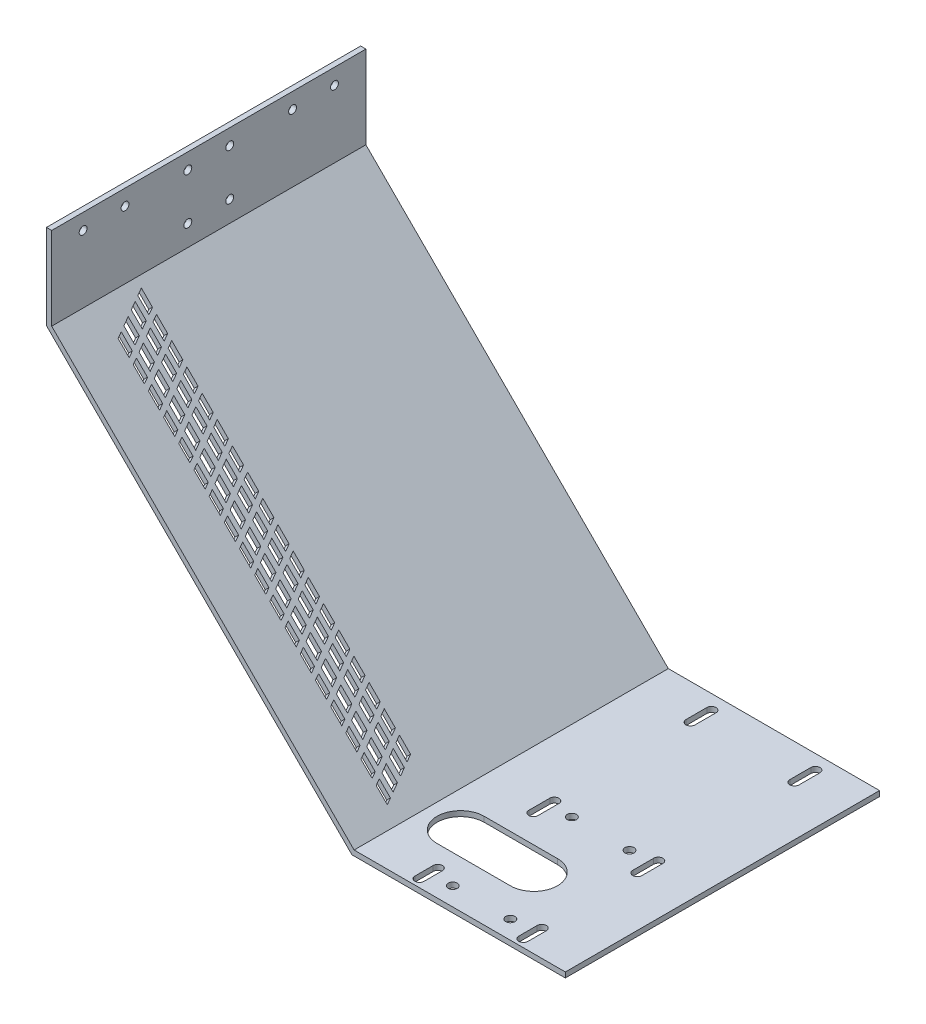
SolidWorks part; units mm, degrees
ref_plane "前视基准面" through (0, 0, 0) normal (0, 0, 1) x (1, 0, 0)
ref_plane "上视基准面" through (0, 0, 0) normal (0, 1, 0) x (1, 0, 0)
ref_plane "右视基准面" through (0, 0, 0) normal (1, 0, 0) x (0, 0, -1)
other "Configuration Table"
sketch "草图1" plane through (0, 0, 0) normal (0, 0, 1) x (1, 0, 0)
  line L0 (-1, -199.1726) -> (-1, -50)
  line L1 (-1, -50) -> (-199.1726, -50)
  line L2 (-199.1726, -50) -> (-199.1726, -82.5)
  line L3 (-199.1726, -82.5) -> (-82.5, -199.1726)
  line L4 (-82.5, -199.1726) -> (-1, -199.1726)
  dimension "D1" = 116.6726
  dimension "D2" = 198.1726
  dimension "D3" = 116.6726
  dimension "D4" = 149.1726
extrude "凸台-拉伸1" add sketch "草图1" against normal blind 120
sketch "草图2" plane through (0, 0, -120) normal (0, 0, -1) x (-1, 0, 0)
  line L0 (197.1726, -81.6716) -> (197.1726, -50)
  line L1 (197.1726, -50) -> (1, -50)
  line L2 (1, -50) -> (1, -197.1726)
  line L3 (1, -197.1726) -> (81.6716, -197.1726)
  line L4 (81.6716, -197.1726) -> (197.1726, -81.6716)
  line L5 (199.1726, -50) -> (199.1726, -82.5) construction
  line L6 (82.5, -199.1726) -> (1, -199.1726) construction
  dimension "D1" = 2
  dimension "D2" = 117.501
  dimension "D3" = 198.1726
  dimension "D4" = 2
  dimension "D5" = 117.501
  dimension "D6" = 149.1726
extrude "切除-拉伸1" cut sketch "草图2" against normal through all
sketch "草图3" plane through (0, -197.1726, 0) normal (0, 1, 0) x (-1, 0, 0)
  line L0 (57.95, -106.5) -> (57.95, -114.5)
  line L1 (61.45, -114.5) -> (61.45, -106.5)
  line L2 (81.6716, 0) -> (81.6716, -120) construction
  line L3 (1, -120) -> (81.6716, -120) construction
  arc A0 (61.45, -106.5) -> (57.95, -106.5) centre (59.7, -106.5) ccw
  arc A1 (57.95, -114.5) -> (61.45, -114.5) centre (59.7, -114.5) ccw
  dimension "D1" = 1.75
  dimension "D2" = 21.9716
  dimension "D3" = 5.5
  dimension "D4" = 13.5
extrude "切除-拉伸2" cut sketch "草图3" against normal through all
sketch "草图4" plane through (0, -197.1726, 0) normal (0, 1, 0) x (-1, 0, 0)
  line L0 (18.25, -106.5) -> (18.25, -114.5)
  line L1 (21.75, -114.5) -> (21.75, -106.5)
  line L2 (61.45, -114.5) -> (61.45, -106.5) construction
  arc A0 (18.25, -114.5) -> (21.75, -114.5) centre (20, -114.5) ccw
  arc A1 (21.75, -106.5) -> (18.25, -106.5) centre (20, -106.5) ccw
  dimension "D1" = 1.75
  dimension "D2" = 41.45
  dimension "D3" = 8
extrude "切除-拉伸3" cut sketch "草图4" against normal through all
sketch "草图5" plane through (0, -197.1726, 0) normal (0, 1, 0) x (-1, 0, 0)
  line L0 (61.45, -54.5) -> (61.45, -46.5)
  line L1 (57.95, -46.5) -> (57.95, -54.5)
  line L2 (18.25, -106.5) -> (18.25, -114.5) construction
  arc A0 (61.45, -46.5) -> (57.95, -46.5) centre (59.7, -46.5) ccw
  arc A1 (57.95, -54.5) -> (61.45, -54.5) centre (59.7, -54.5) ccw
  dimension "D1" = 1.75
  dimension "D2" = 41.45
  dimension "D3" = 52
  dimension "D4" = 60
extrude "切除-拉伸4" cut sketch "草图5" against normal through all
sketch "草图6" plane through (0, -197.1726, 0) normal (0, 1, 0) x (-1, 0, 0)
  line L0 (21.75, -54.5) -> (21.75, -46.5)
  line L1 (18.25, -46.5) -> (18.25, -54.5)
  line L2 (61.45, -54.5) -> (61.45, -46.5) construction
  arc A0 (18.25, -54.5) -> (21.75, -54.5) centre (20, -54.5) ccw
  arc A1 (21.75, -46.5) -> (18.25, -46.5) centre (20, -46.5) ccw
  dimension "D1" = 1.75
  dimension "D2" = 41.45
  dimension "D3" = 52
  dimension "D4" = 60
extrude "切除-拉伸5" cut sketch "草图6" against normal through all
sketch "草图7" plane through (0, -197.1726, 0) normal (0, 1, 0) x (-1, 0, 0)
  line L0 (61.45, -10) -> (61.45, -3)
  line L1 (57.95, -3) -> (57.95, -10)
  line L2 (61.45, -54.5) -> (61.45, -46.5) construction
  arc A0 (61.45, -3) -> (57.95, -3) centre (59.7, -3) ccw
  arc A1 (57.95, -10) -> (61.45, -10) centre (59.7, -10) ccw
  dimension "D1" = 1.75
  dimension "D2" = 1.75
  dimension "D3" = 96.5
  dimension "D4" = 103.5
extrude "切除-拉伸6" cut sketch "草图7" against normal through all
sketch "草图8" plane through (0, -197.1726, 0) normal (0, 1, 0) x (-1, 0, 0)
  line L0 (18.25, -3) -> (18.25, -10)
  line L1 (21.75, -10) -> (21.75, -3)
  line L2 (61.45, -54.5) -> (61.45, -46.5) construction
  arc A0 (18.25, -10) -> (21.75, -10) centre (20, -10) ccw
  arc A1 (21.75, -3) -> (18.25, -3) centre (20, -3) ccw
  dimension "D1" = 1.75
  dimension "D2" = 41.45
  dimension "D3" = 44.5
  dimension "D4" = 51.5
extrude "切除-拉伸7" cut sketch "草图8" against normal through all
sketch "草图9" plane through (-139.4221, -139.4221, 0) normal (0.7071, 0.7071, 0) x (-0.7071, 0.7071, 0)
  line L0 (-55.0094, -28) -> (-56.4528, -25.5)
  line L1 (-56.4528, -25.5) -> (-62.4528, -25.5)
  line L2 (-62.4528, -25.5) -> (-61.0094, -28)
  line L3 (-61.0094, -28) -> (-55.0094, -28)
  line L4 (81.6716, 0) -> (81.6716, -120) construction
  dimension "D1" = 136.681
  dimension "D2" = 138.1243
  dimension "D3" = 142.681
  dimension "D4" = 144.1243
  dimension "D5" = 25.5
  dimension "D6" = 28
extrude "切除-拉伸8" cut sketch "草图9" against normal through all
sketch "草图10" plane through (-139.4221, -139.4221, 0) normal (0.7071, 0.7071, 0) x (-0.7071, 0.7071, 0)
  line L0 (-57.6075, -23.5) -> (-59.2056, -20.7321)
  line L1 (-59.2056, -20.7321) -> (-65.2056, -20.7321)
  line L2 (-65.2056, -20.7321) -> (-63.6075, -23.5)
  line L3 (-63.6075, -23.5) -> (-57.6075, -23.5)
  dimension "D1" = 2.5981
  dimension "D2" = 4.1962
  dimension "D3" = 8.5981
  dimension "D4" = 10.1962
  dimension "D5" = 2
  dimension "D6" = 4.7679
extrude "切除-拉伸9" cut sketch "草图10" against normal through all
sketch "草图11" plane through (-139.4221, -139.4221, 0) normal (0.7071, 0.7071, 0) x (-0.7071, 0.7071, 0)
  line L0 (-51.8094, -29.7321) -> (-50.5, -32)
  line L1 (-50.5, -32) -> (-44.5, -32)
  line L2 (-44.5, -32) -> (-45.8094, -29.7321)
  line L3 (-45.8094, -29.7321) -> (-51.8094, -29.7321)
  dimension "D1" = 13.3962
  dimension "D2" = 14.7056
  dimension "D3" = 19.3962
  dimension "D4" = 20.7056
  dimension "D5" = 1.7321
  dimension "D6" = 4
extrude "切除-拉伸10" cut sketch "草图11" against normal through all
sketch "草图12" plane through (-139.4221, -139.4221, 0) normal (0.7071, 0.7071, 0) x (-0.7071, 0.7071, 0)
  line L0 (-46.8094, -28) -> (-48.2528, -25.5)
  line L1 (-48.2528, -25.5) -> (-54.2528, -25.5)
  line L2 (-54.2528, -25.5) -> (-52.8094, -28)
  line L3 (-52.8094, -28) -> (-46.8094, -28)
  dimension "D1" = 2.3094
  dimension "D2" = 3.7528
  dimension "D3" = 8.3094
  dimension "D4" = 9.7528
  dimension "D5" = 4.7679
  dimension "D6" = 7.2679
extrude "切除-拉伸11" cut sketch "草图12" against normal through all
sketch "草图13" plane through (-139.4221, -139.4221, 0) normal (0.7071, 0.7071, 0) x (-0.7071, 0.7071, 0)
  line L0 (-49.4075, -23.5) -> (-51.0056, -20.7321)
  line L1 (-51.0056, -20.7321) -> (-57.0056, -20.7321)
  line L2 (-57.0056, -20.7321) -> (-55.4075, -23.5)
  line L3 (-55.4075, -23.5) -> (-49.4075, -23.5)
  dimension "D1" = 6.6019
  dimension "D2" = 8.2
  dimension "D3" = 12.6019
  dimension "D4" = 14.2
  dimension "D5" = 8.5
  dimension "D6" = 11.2679
extrude "切除-拉伸12" cut sketch "草图13" against normal through all
sketch "草图14" plane through (-139.4221, -139.4221, 0) normal (0.7071, 0.7071, 0) x (-0.7071, 0.7071, 0)
  line L0 (-43.6094, -29.7321) -> (-42.3, -32)
  line L1 (-42.3, -32) -> (-36.3, -32)
  line L2 (-36.3, -32) -> (-37.6094, -29.7321)
  line L3 (-37.6094, -29.7321) -> (-43.6094, -29.7321)
  dimension "D1" = 0.8906
  dimension "D2" = 2.2
  dimension "D3" = 6.8906
  dimension "D4" = 8.2
  dimension "D5" = 9
  dimension "D6" = 11.2679
extrude "切除-拉伸13" cut sketch "草图14" against normal through all
sketch "草图15" plane through (-139.4221, -139.4221, 0) normal (0.7071, 0.7071, 0) x (-0.7071, 0.7071, 0)
  line L0 (-38.6094, -28) -> (-40.0528, -25.5)
  line L1 (-40.0528, -25.5) -> (-46.0528, -25.5)
  line L2 (-46.0528, -25.5) -> (-44.6094, -28)
  line L3 (-44.6094, -28) -> (-38.6094, -28)
  dimension "D1" = 10.9528
  dimension "D2" = 12.3962
  dimension "D3" = 16.9528
  dimension "D4" = 18.3962
  dimension "D5" = 4
  dimension "D6" = 6.5
extrude "切除-拉伸14" cut sketch "草图15" against normal through all
sketch "草图16" plane through (-139.4221, -139.4221, 0) normal (0.7071, 0.7071, 0) x (-0.7071, 0.7071, 0)
  line L0 (-41.2075, -23.5) -> (-42.8056, -20.7321)
  line L1 (-42.8056, -20.7321) -> (-48.8056, -20.7321)
  line L2 (-48.8056, -20.7321) -> (-47.2075, -23.5)
  line L3 (-47.2075, -23.5) -> (-41.2075, -23.5)
  dimension "D1" = 4.9075
  dimension "D2" = 6.5056
  dimension "D3" = 10.9075
  dimension "D4" = 12.5056
  dimension "D5" = 2.7679
extrude "切除-拉伸15" cut sketch "草图16" against normal through all
sketch "草图17" plane through (-139.4221, -139.4221, 0) normal (0.7071, 0.7071, 0) x (-0.7071, 0.7071, 0)
  line L0 (-35.4094, -29.7321) -> (-34.1, -32)
  line L1 (-34.1, -32) -> (-28.1, -32)
  line L2 (-28.1, -32) -> (-29.4094, -29.7321)
  line L3 (-29.4094, -29.7321) -> (-35.4094, -29.7321)
  dimension "D1" = 21.5962
  dimension "D2" = 22.9056
  dimension "D3" = 27.5962
  dimension "D4" = 28.9056
  dimension "D5" = 2.2679
extrude "切除-拉伸16" cut sketch "草图17" against normal through all
sketch "草图18" plane through (-139.4221, -139.4221, 0) normal (0.7071, 0.7071, 0) x (-0.7071, 0.7071, 0)
  line L0 (-30.4094, -28) -> (-31.8528, -25.5)
  line L1 (-31.8528, -25.5) -> (-37.8528, -25.5)
  line L2 (-37.8528, -25.5) -> (-36.4094, -28)
  line L3 (-36.4094, -28) -> (-30.4094, -28)
  dimension "D1" = 2.3094
  dimension "D2" = 3.7528
  dimension "D3" = 8.3094
  dimension "D4" = 9.7528
  dimension "D5" = 4.7679
  dimension "D6" = 7.2679
extrude "切除-拉伸17" cut sketch "草图18" against normal through all
sketch "草图19" plane through (-139.4221, -139.4221, 0) normal (0.7071, 0.7071, 0) x (-0.7071, 0.7071, 0)
  line L0 (-33.0075, -23.5) -> (-34.6056, -20.7321)
  line L1 (-34.6056, -20.7321) -> (-40.6056, -20.7321)
  line L2 (-40.6056, -20.7321) -> (-39.0075, -23.5)
  line L3 (-39.0075, -23.5) -> (-33.0075, -23.5)
  dimension "D1" = 14.8019
  dimension "D2" = 16.4
  dimension "D3" = 20.8019
  dimension "D4" = 22.4
  dimension "D5" = 8.5
  dimension "D6" = 11.2679
extrude "切除-拉伸18" cut sketch "草图19" against normal through all
sketch "草图20" plane through (-139.4221, -139.4221, 0) normal (0.7071, 0.7071, 0) x (-0.7071, 0.7071, 0)
  line L0 (-27.2094, -29.7321) -> (-25.9, -32)
  line L1 (-25.9, -32) -> (-19.9, -32)
  line L2 (-19.9, -32) -> (-21.2094, -29.7321)
  line L3 (-21.2094, -29.7321) -> (-27.2094, -29.7321)
  dimension "D1" = 0.8906
  dimension "D2" = 2.2
  dimension "D3" = 6.8906
  dimension "D4" = 8.2
  dimension "D5" = 9
  dimension "D6" = 11.2679
extrude "切除-拉伸19" cut sketch "草图20" against normal through all
sketch "草图21" plane through (-139.4221, -139.4221, 0) normal (0.7071, 0.7071, 0) x (-0.7071, 0.7071, 0)
  line L0 (-22.2094, -28) -> (-23.6528, -25.5)
  line L1 (-23.6528, -25.5) -> (-29.6528, -25.5)
  line L2 (-29.6528, -25.5) -> (-28.2094, -28)
  line L3 (-28.2094, -28) -> (-22.2094, -28)
  dimension "D1" = 19.1528
  dimension "D2" = 20.5962
  dimension "D3" = 25.1528
  dimension "D4" = 26.5962
  dimension "D5" = 4
  dimension "D6" = 6.5
extrude "切除-拉伸20" cut sketch "草图21" against normal through all
sketch "草图22" plane through (-139.4221, -139.4221, 0) normal (0.7071, 0.7071, 0) x (-0.7071, 0.7071, 0)
  line L0 (-24.8075, -23.5) -> (-26.4056, -20.7321)
  line L1 (-26.4056, -20.7321) -> (-32.4056, -20.7321)
  line L2 (-32.4056, -20.7321) -> (-30.8075, -23.5)
  line L3 (-30.8075, -23.5) -> (-24.8075, -23.5)
  dimension "D1" = 4.9075
  dimension "D2" = 6.5056
  dimension "D3" = 10.9075
  dimension "D4" = 12.5056
  dimension "D5" = 2.7679
extrude "切除-拉伸21" cut sketch "草图22" against normal through all
sketch "草图23" plane through (-139.4221, -139.4221, 0) normal (0.7071, 0.7071, 0) x (-0.7071, 0.7071, 0)
  line L0 (-19.0094, -29.7321) -> (-17.7, -32)
  line L1 (-17.7, -32) -> (-11.7, -32)
  line L2 (-11.7, -32) -> (-13.0094, -29.7321)
  line L3 (-13.0094, -29.7321) -> (-19.0094, -29.7321)
  dimension "D1" = 29.7962
  dimension "D2" = 31.1056
  dimension "D3" = 35.7962
  dimension "D4" = 37.1056
  dimension "D5" = 2.2679
extrude "切除-拉伸22" cut sketch "草图23" against normal through all
sketch "草图24" plane through (-139.4221, -139.4221, 0) normal (0.7071, 0.7071, 0) x (-0.7071, 0.7071, 0)
  line L0 (-14.0094, -28) -> (-15.4528, -25.5)
  line L1 (-15.4528, -25.5) -> (-21.4528, -25.5)
  line L2 (-21.4528, -25.5) -> (-20.0094, -28)
  line L3 (-20.0094, -28) -> (-14.0094, -28)
  dimension "D1" = 2.3094
  dimension "D2" = 3.7528
  dimension "D3" = 8.3094
  dimension "D4" = 9.7528
  dimension "D5" = 4.7679
  dimension "D6" = 7.2679
extrude "切除-拉伸23" cut sketch "草图24" against normal through all
sketch "草图25" plane through (-139.4221, -139.4221, 0) normal (0.7071, 0.7071, 0) x (-0.7071, 0.7071, 0)
  line L0 (-16.6075, -23.5) -> (-18.2056, -20.7321)
  line L1 (-18.2056, -20.7321) -> (-24.2056, -20.7321)
  line L2 (-24.2056, -20.7321) -> (-22.6075, -23.5)
  line L3 (-22.6075, -23.5) -> (-16.6075, -23.5)
  dimension "D1" = 23.0019
  dimension "D2" = 24.6
  dimension "D3" = 29.0019
  dimension "D4" = 30.6
  dimension "D5" = 8.5
  dimension "D6" = 11.2679
extrude "切除-拉伸24" cut sketch "草图25" against normal through all
sketch "草图26" plane through (-139.4221, -139.4221, 0) normal (0.7071, 0.7071, 0) x (-0.7071, 0.7071, 0)
  line L0 (-10.8094, -29.7321) -> (-9.5, -32)
  line L1 (-9.5, -32) -> (-3.5, -32)
  line L2 (-3.5, -32) -> (-4.8094, -29.7321)
  line L3 (-4.8094, -29.7321) -> (-10.8094, -29.7321)
  dimension "D1" = 0.8906
  dimension "D2" = 2.2
  dimension "D3" = 6.8906
  dimension "D4" = 8.2
  dimension "D5" = 9
  dimension "D6" = 11.2679
extrude "切除-拉伸25" cut sketch "草图26" against normal through all
sketch "草图27" plane through (-139.4221, -139.4221, 0) normal (0.7071, 0.7071, 0) x (-0.7071, 0.7071, 0)
  line L0 (-5.8094, -28) -> (-7.2528, -25.5)
  line L1 (-7.2528, -25.5) -> (-13.2528, -25.5)
  line L2 (-13.2528, -25.5) -> (-11.8094, -28)
  line L3 (-11.8094, -28) -> (-5.8094, -28)
  dimension "D1" = 27.3528
  dimension "D2" = 28.7962
  dimension "D3" = 33.3528
  dimension "D4" = 34.7962
  dimension "D5" = 4
  dimension "D6" = 6.5
extrude "切除-拉伸26" cut sketch "草图27" against normal through all
sketch "草图28" plane through (-139.4221, -139.4221, 0) normal (0.7071, 0.7071, 0) x (-0.7071, 0.7071, 0)
  line L0 (-8.4075, -23.5) -> (-10.0056, -20.7321)
  line L1 (-10.0056, -20.7321) -> (-16.0056, -20.7321)
  line L2 (-16.0056, -20.7321) -> (-14.4075, -23.5)
  line L3 (-14.4075, -23.5) -> (-8.4075, -23.5)
  dimension "D1" = 4.9075
  dimension "D2" = 6.5056
  dimension "D3" = 10.9075
  dimension "D4" = 12.5056
  dimension "D5" = 2.7679
extrude "切除-拉伸27" cut sketch "草图28" against normal through all
sketch "草图29" plane through (-139.4221, -139.4221, 0) normal (0.7071, 0.7071, 0) x (-0.7071, 0.7071, 0)
  line L0 (-2.6094, -29.7321) -> (-1.3, -32)
  line L1 (-1.3, -32) -> (4.7, -32)
  line L2 (4.7, -32) -> (3.3906, -29.7321)
  line L3 (3.3906, -29.7321) -> (-2.6094, -29.7321)
  dimension "D1" = 37.9962
  dimension "D2" = 39.3056
  dimension "D3" = 43.9962
  dimension "D4" = 45.3056
  dimension "D5" = 2.2679
extrude "切除-拉伸28" cut sketch "草图29" against normal through all
sketch "草图30" plane through (-139.4221, -139.4221, 0) normal (0.7071, 0.7071, 0) x (-0.7071, 0.7071, 0)
  line L0 (2.3906, -28) -> (0.9472, -25.5)
  line L1 (0.9472, -25.5) -> (-5.0528, -25.5)
  line L2 (-5.0528, -25.5) -> (-3.6094, -28)
  line L3 (-3.6094, -28) -> (2.3906, -28)
  dimension "D1" = 2.3094
  dimension "D2" = 3.7528
  dimension "D3" = 8.3094
  dimension "D4" = 9.7528
  dimension "D5" = 4.7679
  dimension "D6" = 7.2679
extrude "切除-拉伸29" cut sketch "草图30" against normal through all
sketch "草图31" plane through (-139.4221, -139.4221, 0) normal (0.7071, 0.7071, 0) x (-0.7071, 0.7071, 0)
  line L0 (-0.2075, -23.5) -> (-1.8056, -20.7321)
  line L1 (-1.8056, -20.7321) -> (-7.8056, -20.7321)
  line L2 (-7.8056, -20.7321) -> (-6.2075, -23.5)
  line L3 (-6.2075, -23.5) -> (-0.2075, -23.5)
  dimension "D1" = 31.2019
  dimension "D2" = 32.8
  dimension "D3" = 37.2019
  dimension "D4" = 38.8
  dimension "D5" = 8.5
  dimension "D6" = 11.2679
extrude "切除-拉伸30" cut sketch "草图31" against normal through all
sketch "草图32" plane through (-139.4221, -139.4221, 0) normal (0.7071, 0.7071, 0) x (-0.7071, 0.7071, 0)
  line L0 (5.5906, -29.7321) -> (6.9, -32)
  line L1 (6.9, -32) -> (12.9, -32)
  line L2 (12.9, -32) -> (11.5906, -29.7321)
  line L3 (11.5906, -29.7321) -> (5.5906, -29.7321)
  dimension "D1" = 0.8906
  dimension "D2" = 2.2
  dimension "D3" = 6.8906
  dimension "D4" = 8.2
  dimension "D5" = 9
  dimension "D6" = 11.2679
extrude "切除-拉伸31" cut sketch "草图32" against normal through all
sketch "草图33" plane through (-139.4221, -139.4221, 0) normal (0.7071, 0.7071, 0) x (-0.7071, 0.7071, 0)
  line L0 (10.5906, -28) -> (9.1472, -25.5)
  line L1 (9.1472, -25.5) -> (3.1472, -25.5)
  line L2 (3.1472, -25.5) -> (4.5906, -28)
  line L3 (4.5906, -28) -> (10.5906, -28)
  dimension "D1" = 35.5528
  dimension "D2" = 36.9962
  dimension "D3" = 41.5528
  dimension "D4" = 42.9962
  dimension "D5" = 4
  dimension "D6" = 6.5
extrude "切除-拉伸32" cut sketch "草图33" against normal through all
sketch "草图34" plane through (-139.4221, -139.4221, 0) normal (0.7071, 0.7071, 0) x (-0.7071, 0.7071, 0)
  line L0 (7.9925, -23.5) -> (6.3944, -20.7321)
  line L1 (6.3944, -20.7321) -> (0.3944, -20.7321)
  line L2 (0.3944, -20.7321) -> (1.9925, -23.5)
  line L3 (1.9925, -23.5) -> (7.9925, -23.5)
  dimension "D1" = 4.9075
  dimension "D2" = 6.5056
  dimension "D3" = 10.9075
  dimension "D4" = 12.5056
  dimension "D5" = 2.7679
extrude "切除-拉伸33" cut sketch "草图34" against normal through all
sketch "草图35" plane through (-139.4221, -139.4221, 0) normal (0.7071, 0.7071, 0) x (-0.7071, 0.7071, 0)
  line L0 (13.7906, -29.7321) -> (15.1, -32)
  line L1 (15.1, -32) -> (21.1, -32)
  line L2 (21.1, -32) -> (19.7906, -29.7321)
  line L3 (19.7906, -29.7321) -> (13.7906, -29.7321)
  dimension "D1" = 46.1962
  dimension "D2" = 47.5056
  dimension "D3" = 52.1962
  dimension "D4" = 53.5056
  dimension "D5" = 2.2679
extrude "切除-拉伸34" cut sketch "草图35" against normal through all
sketch "草图36" plane through (-139.4221, -139.4221, 0) normal (0.7071, 0.7071, 0) x (-0.7071, 0.7071, 0)
  line L0 (18.7906, -28) -> (17.3472, -25.5)
  line L1 (17.3472, -25.5) -> (11.3472, -25.5)
  line L2 (11.3472, -25.5) -> (12.7906, -28)
  line L3 (12.7906, -28) -> (18.7906, -28)
  dimension "D1" = 2.3094
  dimension "D2" = 3.7528
  dimension "D3" = 8.3094
  dimension "D4" = 9.7528
  dimension "D5" = 4.7679
  dimension "D6" = 7.2679
extrude "切除-拉伸35" cut sketch "草图36" against normal through all
sketch "草图37" plane through (-139.4221, -139.4221, 0) normal (0.7071, 0.7071, 0) x (-0.7071, 0.7071, 0)
  line L0 (16.1925, -23.5) -> (14.5944, -20.7321)
  line L1 (14.5944, -20.7321) -> (8.5944, -20.7321)
  line L2 (8.5944, -20.7321) -> (10.1925, -23.5)
  line L3 (10.1925, -23.5) -> (16.1925, -23.5)
  dimension "D1" = 39.4019
  dimension "D2" = 41
  dimension "D3" = 45.4019
  dimension "D4" = 47
  dimension "D5" = 8.5
  dimension "D6" = 11.2679
extrude "切除-拉伸36" cut sketch "草图37" against normal through all
sketch "草图38" plane through (-139.4221, -139.4221, 0) normal (0.7071, 0.7071, 0) x (-0.7071, 0.7071, 0)
  line L0 (21.9906, -29.7321) -> (23.3, -32)
  line L1 (23.3, -32) -> (29.3, -32)
  line L2 (29.3, -32) -> (27.9906, -29.7321)
  line L3 (27.9906, -29.7321) -> (21.9906, -29.7321)
  dimension "D1" = 0.8906
  dimension "D2" = 2.2
  dimension "D3" = 6.8906
  dimension "D4" = 8.2
  dimension "D5" = 9
  dimension "D6" = 11.2679
extrude "切除-拉伸37" cut sketch "草图38" against normal through all
sketch "草图39" plane through (-139.4221, -139.4221, 0) normal (0.7071, 0.7071, 0) x (-0.7071, 0.7071, 0)
  line L0 (26.9906, -28) -> (25.5472, -25.5)
  line L1 (25.5472, -25.5) -> (19.5472, -25.5)
  line L2 (19.5472, -25.5) -> (20.9906, -28)
  line L3 (20.9906, -28) -> (26.9906, -28)
  dimension "D1" = 43.7528
  dimension "D2" = 45.1962
  dimension "D3" = 49.7528
  dimension "D4" = 51.1962
  dimension "D5" = 4
  dimension "D6" = 6.5
extrude "切除-拉伸38" cut sketch "草图39" against normal through all
sketch "草图40" plane through (-139.4221, -139.4221, 0) normal (0.7071, 0.7071, 0) x (-0.7071, 0.7071, 0)
  line L0 (24.3925, -23.5) -> (22.7944, -20.7321)
  line L1 (22.7944, -20.7321) -> (16.7944, -20.7321)
  line L2 (16.7944, -20.7321) -> (18.3925, -23.5)
  line L3 (18.3925, -23.5) -> (24.3925, -23.5)
  dimension "D1" = 4.9075
  dimension "D2" = 6.5056
  dimension "D3" = 10.9075
  dimension "D4" = 12.5056
  dimension "D5" = 2.7679
extrude "切除-拉伸39" cut sketch "草图40" against normal through all
sketch "草图41" plane through (-139.4221, -139.4221, 0) normal (0.7071, 0.7071, 0) x (-0.7071, 0.7071, 0)
  line L0 (30.1906, -29.7321) -> (31.5, -32)
  line L1 (31.5, -32) -> (37.5, -32)
  line L2 (37.5, -32) -> (36.1906, -29.7321)
  line L3 (36.1906, -29.7321) -> (30.1906, -29.7321)
  dimension "D1" = 54.3962
  dimension "D2" = 55.7056
  dimension "D3" = 60.3962
  dimension "D4" = 61.7056
  dimension "D5" = 2.2679
extrude "切除-拉伸40" cut sketch "草图41" against normal through all
sketch "草图42" plane through (-139.4221, -139.4221, 0) normal (0.7071, 0.7071, 0) x (-0.7071, 0.7071, 0)
  line L0 (35.1906, -28) -> (33.7472, -25.5)
  line L1 (33.7472, -25.5) -> (27.7472, -25.5)
  line L2 (27.7472, -25.5) -> (29.1906, -28)
  line L3 (29.1906, -28) -> (35.1906, -28)
  dimension "D1" = 2.3094
  dimension "D2" = 3.7528
  dimension "D3" = 8.3094
  dimension "D4" = 9.7528
  dimension "D5" = 4.7679
  dimension "D6" = 7.2679
extrude "切除-拉伸41" cut sketch "草图42" against normal through all
sketch "草图43" plane through (-139.4221, -139.4221, 0) normal (0.7071, 0.7071, 0) x (-0.7071, 0.7071, 0)
  line L0 (32.5925, -23.5) -> (30.9944, -20.7321)
  line L1 (30.9944, -20.7321) -> (24.9944, -20.7321)
  line L2 (24.9944, -20.7321) -> (26.5925, -23.5)
  line L3 (26.5925, -23.5) -> (32.5925, -23.5)
  dimension "D1" = 47.6019
  dimension "D2" = 49.2
  dimension "D3" = 53.6019
  dimension "D4" = 55.2
  dimension "D5" = 8.5
  dimension "D6" = 11.2679
extrude "切除-拉伸42" cut sketch "草图43" against normal through all
sketch "草图44" plane through (-139.4221, -139.4221, 0) normal (0.7071, 0.7071, 0) x (-0.7071, 0.7071, 0)
  line L0 (38.3906, -29.7321) -> (39.7, -32)
  line L1 (39.7, -32) -> (45.7, -32)
  line L2 (45.7, -32) -> (44.3906, -29.7321)
  line L3 (44.3906, -29.7321) -> (38.3906, -29.7321)
  dimension "D1" = 0.8906
  dimension "D2" = 2.2
  dimension "D3" = 6.8906
  dimension "D4" = 8.2
  dimension "D5" = 9
  dimension "D6" = 11.2679
extrude "切除-拉伸43" cut sketch "草图44" against normal through all
sketch "草图45" plane through (-139.4221, -139.4221, 0) normal (0.7071, 0.7071, 0) x (-0.7071, 0.7071, 0)
  line L0 (43.3906, -28) -> (41.9472, -25.5)
  line L1 (41.9472, -25.5) -> (35.9472, -25.5)
  line L2 (35.9472, -25.5) -> (37.3906, -28)
  line L3 (37.3906, -28) -> (43.3906, -28)
  dimension "D1" = 51.9528
  dimension "D2" = 53.3962
  dimension "D3" = 57.9528
  dimension "D4" = 59.3962
  dimension "D5" = 4
  dimension "D6" = 6.5
extrude "切除-拉伸44" cut sketch "草图45" against normal through all
sketch "草图46" plane through (-139.4221, -139.4221, 0) normal (0.7071, 0.7071, 0) x (-0.7071, 0.7071, 0)
  line L0 (40.7925, -23.5) -> (39.1944, -20.7321)
  line L1 (39.1944, -20.7321) -> (33.1944, -20.7321)
  line L2 (33.1944, -20.7321) -> (34.7925, -23.5)
  line L3 (34.7925, -23.5) -> (40.7925, -23.5)
  dimension "D1" = 4.9075
  dimension "D2" = 6.5056
  dimension "D3" = 10.9075
  dimension "D4" = 12.5056
  dimension "D5" = 2.7679
extrude "切除-拉伸45" cut sketch "草图46" against normal through all
sketch "草图47" plane through (-139.4221, -139.4221, 0) normal (0.7071, 0.7071, 0) x (-0.7071, 0.7071, 0)
  line L0 (46.5906, -29.7321) -> (47.9, -32)
  line L1 (47.9, -32) -> (53.9, -32)
  line L2 (53.9, -32) -> (52.5906, -29.7321)
  line L3 (52.5906, -29.7321) -> (46.5906, -29.7321)
  dimension "D1" = 62.5962
  dimension "D2" = 63.9056
  dimension "D3" = 68.5962
  dimension "D4" = 69.9056
  dimension "D5" = 2.2679
extrude "切除-拉伸46" cut sketch "草图47" against normal through all
sketch "草图48" plane through (-139.4221, -139.4221, 0) normal (0.7071, 0.7071, 0) x (-0.7071, 0.7071, 0)
  line L0 (51.5906, -28) -> (50.1472, -25.5)
  line L1 (50.1472, -25.5) -> (44.1472, -25.5)
  line L2 (44.1472, -25.5) -> (45.5906, -28)
  line L3 (45.5906, -28) -> (51.5906, -28)
  dimension "D1" = 2.3094
  dimension "D2" = 3.7528
  dimension "D3" = 8.3094
  dimension "D4" = 9.7528
  dimension "D5" = 4.7679
  dimension "D6" = 7.2679
extrude "切除-拉伸47" cut sketch "草图48" against normal through all
sketch "草图49" plane through (-139.4221, -139.4221, 0) normal (0.7071, 0.7071, 0) x (-0.7071, 0.7071, 0)
  line L0 (48.9925, -23.5) -> (47.3944, -20.7321)
  line L1 (47.3944, -20.7321) -> (41.3944, -20.7321)
  line L2 (41.3944, -20.7321) -> (42.9925, -23.5)
  line L3 (42.9925, -23.5) -> (48.9925, -23.5)
  dimension "D1" = 55.8019
  dimension "D2" = 57.4
  dimension "D3" = 61.8019
  dimension "D4" = 63.4
  dimension "D5" = 8.5
  dimension "D6" = 11.2679
extrude "切除-拉伸48" cut sketch "草图49" against normal through all
sketch "草图50" plane through (-139.4221, -139.4221, 0) normal (0.7071, 0.7071, 0) x (-0.7071, 0.7071, 0)
  line L0 (54.7906, -29.7321) -> (56.1, -32)
  line L1 (56.1, -32) -> (62.1, -32)
  line L2 (62.1, -32) -> (60.7906, -29.7321)
  line L3 (60.7906, -29.7321) -> (54.7906, -29.7321)
  dimension "D1" = 0.8906
  dimension "D2" = 2.2
  dimension "D3" = 6.8906
  dimension "D4" = 8.2
  dimension "D5" = 9
  dimension "D6" = 11.2679
extrude "切除-拉伸49" cut sketch "草图50" against normal through all
sketch "草图51" plane through (-139.4221, -139.4221, 0) normal (0.7071, 0.7071, 0) x (-0.7071, 0.7071, 0)
  line L0 (59.7906, -28) -> (58.3472, -25.5)
  line L1 (58.3472, -25.5) -> (52.3472, -25.5)
  line L2 (52.3472, -25.5) -> (53.7906, -28)
  line L3 (53.7906, -28) -> (59.7906, -28)
  dimension "D1" = 60.1528
  dimension "D2" = 61.5962
  dimension "D3" = 66.1528
  dimension "D4" = 67.5962
  dimension "D5" = 4
  dimension "D6" = 6.5
extrude "切除-拉伸50" cut sketch "草图51" against normal through all
sketch "草图52" plane through (-139.4221, -139.4221, 0) normal (0.7071, 0.7071, 0) x (-0.7071, 0.7071, 0)
  line L0 (57.1925, -23.5) -> (55.5944, -20.7321)
  line L1 (55.5944, -20.7321) -> (49.5944, -20.7321)
  line L2 (49.5944, -20.7321) -> (51.1925, -23.5)
  line L3 (51.1925, -23.5) -> (57.1925, -23.5)
  dimension "D1" = 4.9075
  dimension "D2" = 6.5056
  dimension "D3" = 10.9075
  dimension "D4" = 12.5056
  dimension "D5" = 2.7679
extrude "切除-拉伸51" cut sketch "草图52" against normal through all
sketch "草图53" plane through (-139.4221, -139.4221, 0) normal (0.7071, 0.7071, 0) x (-0.7071, 0.7071, 0)
  line L0 (-68.4056, -19) -> (-69.5603, -17)
  line L1 (-69.5603, -17) -> (-75.5603, -17)
  line L2 (-75.5603, -17) -> (-74.4056, -19)
  line L3 (-74.4056, -19) -> (-68.4056, -19)
  dimension "D1" = 60.6
  dimension "D2" = 61.7547
  dimension "D3" = 66.6
  dimension "D4" = 67.7547
  dimension "D5" = 13
  dimension "D6" = 15
extrude "切除-拉伸52" cut sketch "草图53" against normal through all
sketch "草图54" plane through (-139.4221, -139.4221, 0) normal (0.7071, 0.7071, 0) x (-0.7071, 0.7071, 0)
  line L0 (62.9906, -29.7321) -> (64.3, -32)
  line L1 (64.3, -32) -> (70.3, -32)
  line L2 (70.3, -32) -> (68.9906, -29.7321)
  line L3 (68.9906, -29.7321) -> (62.9906, -29.7321)
  dimension "D1" = 0.8906
  dimension "D2" = 2.2
  dimension "D3" = 6.8906
  dimension "D4" = 8.2
  dimension "D5" = 12.7321
  dimension "D6" = 15
extrude "切除-拉伸53" cut sketch "草图54" against normal through all
sketch "草图55" plane through (-139.4221, -139.4221, 0) normal (0.7071, 0.7071, 0) x (-0.7071, 0.7071, 0)
  line L0 (67.9906, -28) -> (66.5472, -25.5)
  line L1 (66.5472, -25.5) -> (60.5472, -25.5)
  line L2 (60.5472, -25.5) -> (61.9906, -28)
  line L3 (61.9906, -28) -> (67.9906, -28)
  dimension "D1" = 136.1075
  dimension "D2" = 137.5509
  dimension "D3" = 142.1075
  dimension "D4" = 143.5509
  dimension "D5" = 4
  dimension "D6" = 6.5
extrude "切除-拉伸54" cut sketch "草图55" against normal through all
sketch "草图56" plane through (-139.4221, -139.4221, 0) normal (0.7071, 0.7071, 0) x (-0.7071, 0.7071, 0)
  line L0 (65.3925, -23.5) -> (63.7944, -20.7321)
  line L1 (63.7944, -20.7321) -> (57.7944, -20.7321)
  line L2 (57.7944, -20.7321) -> (59.3925, -23.5)
  line L3 (59.3925, -23.5) -> (65.3925, -23.5)
  dimension "D1" = 4.9075
  dimension "D2" = 6.5056
  dimension "D3" = 10.9075
  dimension "D4" = 12.5056
  dimension "D5" = 3.7321
  dimension "D6" = 6.5
extrude "切除-拉伸55" cut sketch "草图56" against normal through all
sketch "草图57" plane through (-139.4221, -139.4221, 0) normal (0.7071, 0.7071, 0) x (-0.7071, 0.7071, 0)
  line L0 (-73.4056, -20.7321) -> (-71.8075, -23.5)
  line L1 (-71.8075, -23.5) -> (-65.8075, -23.5)
  line L2 (-65.8075, -23.5) -> (-67.4056, -20.7321)
  line L3 (-67.4056, -20.7321) -> (-73.4056, -20.7321)
  dimension "D1" = 2.1547
  dimension "D2" = 3.7528
  dimension "D3" = 8.1547
  dimension "D4" = 9.7528
  dimension "D5" = 8.5
  dimension "D6" = 11.2679
extrude "切除-拉伸56" cut sketch "草图57" against normal through all
sketch "草图58" plane through (-139.4221, -139.4221, 0) normal (0.7071, 0.7071, 0) x (-0.7071, 0.7071, 0)
  line L0 (-70.6528, -25.5) -> (-69.2094, -28)
  line L1 (-69.2094, -28) -> (-63.2094, -28)
  line L2 (-63.2094, -28) -> (-64.6528, -25.5)
  line L3 (-64.6528, -25.5) -> (-70.6528, -25.5)
  dimension "D1" = 133.5094
  dimension "D2" = 134.9528
  dimension "D3" = 139.5094
  dimension "D4" = 140.9528
  dimension "D5" = 8.5
  dimension "D6" = 11
extrude "切除-拉伸57" cut sketch "草图58" against normal through all
sketch "草图59" plane through (-139.4221, -139.4221, 0) normal (0.7071, 0.7071, 0) x (-0.7071, 0.7071, 0)
  line L0 (65.9944, -20.7321) -> (67.5925, -23.5)
  line L1 (67.5925, -23.5) -> (73.5925, -23.5)
  line L2 (73.5925, -23.5) -> (71.9944, -20.7321)
  line L3 (71.9944, -20.7321) -> (65.9944, -20.7321)
  dimension "D1" = 141.5547
  dimension "D2" = 143.1528
  dimension "D3" = 147.5547
  dimension "D4" = 149.1528
  dimension "D5" = 8.5
  dimension "D6" = 11.2679
extrude "切除-拉伸58" cut sketch "草图59" against normal through all
sketch "草图60" plane through (-139.4221, -139.4221, 0) normal (0.7071, 0.7071, 0) x (-0.7071, 0.7071, 0)
  line L0 (68.7472, -25.5) -> (70.1906, -28)
  line L1 (70.1906, -28) -> (76.1906, -28)
  line L2 (76.1906, -28) -> (74.7472, -25.5)
  line L3 (74.7472, -25.5) -> (68.7472, -25.5)
  dimension "D1" = 1.1547
  dimension "D2" = 2.5981
  dimension "D3" = 3.4019
  dimension "D4" = 4.8453
  dimension "D5" = 8.5
  dimension "D6" = 11
extrude "切除-拉伸59" cut sketch "草图60" against normal through all
sketch "草图61" plane through (-139.4221, -139.4221, 0) normal (0.7071, 0.7071, 0) x (-0.7071, 0.7071, 0)
  line L0 (71.1906, -29.7321) -> (72.5, -32)
  line L1 (72.5, -32) -> (78.5, -32)
  line L2 (78.5, -32) -> (77.1906, -29.7321)
  line L3 (77.1906, -29.7321) -> (71.1906, -29.7321)
  dimension "D1" = 146.7509
  dimension "D2" = 148.0603
  dimension "D3" = 152.7509
  dimension "D4" = 154.0603
  dimension "D5" = 1.7321
  dimension "D6" = 4
extrude "切除-拉伸60" cut sketch "草图61" against normal through all
sketch "草图62" plane through (-139.4221, -139.4221, 0) normal (0.7071, 0.7071, 0) x (-0.7071, 0.7071, 0)
  line L0 (-60.0094, -29.7321) -> (-58.7, -32)
  line L1 (-58.7, -32) -> (-52.7, -32)
  line L2 (-52.7, -32) -> (-54.0094, -29.7321)
  line L3 (-54.0094, -29.7321) -> (-60.0094, -29.7321)
  dimension "D1" = 131.2
  dimension "D2" = 132.5094
  dimension "D3" = 137.2
  dimension "D4" = 138.5094
  dimension "D5" = 12.7321
  dimension "D6" = 15
extrude "切除-拉伸61" cut sketch "草图62" against normal through all
sketch "草图63" plane through (-139.4221, -139.4221, 0) normal (0.7071, 0.7071, 0) x (-0.7071, 0.7071, 0)
  line L0 (70.9944, -19) -> (69.8397, -17)
  line L1 (69.8397, -17) -> (63.8397, -17)
  line L2 (63.8397, -17) -> (64.9944, -19)
  line L3 (64.9944, -19) -> (70.9944, -19)
  dimension "D1" = 139.4
  dimension "D2" = 140.5547
  dimension "D3" = 145.4
  dimension "D4" = 146.5547
  dimension "D5" = 13
  dimension "D6" = 15
extrude "切除-拉伸62" cut sketch "草图63" against normal through all
sketch "草图64" plane through (-139.4221, -139.4221, 0) normal (0.7071, 0.7071, 0) x (-0.7071, 0.7071, 0)
  line L0 (-68.2094, -29.7321) -> (-66.9, -32)
  line L1 (-66.9, -32) -> (-60.9, -32)
  line L2 (-60.9, -32) -> (-62.2094, -29.7321)
  line L3 (-62.2094, -29.7321) -> (-68.2094, -29.7321)
  dimension "D1" = 139.4
  dimension "D2" = 140.7094
  dimension "D3" = 145.4
  dimension "D4" = 146.7094
  dimension "D5" = 12.7321
  dimension "D6" = 15
extrude "切除-拉伸63" cut sketch "草图64" against normal through all
sketch "草图65" plane through (-139.4221, -139.4221, 0) normal (0.7071, 0.7071, 0) x (-0.7071, 0.7071, 0)
  line L0 (62.7944, -19) -> (61.6397, -17)
  line L1 (61.6397, -17) -> (55.6397, -17)
  line L2 (55.6397, -17) -> (56.7944, -19)
  line L3 (56.7944, -19) -> (62.7944, -19)
  dimension "D1" = 131.2
  dimension "D2" = 132.3547
  dimension "D3" = 137.2
  dimension "D4" = 138.3547
  dimension "D5" = 13
  dimension "D6" = 15
extrude "切除-拉伸64" cut sketch "草图65" against normal through all
sketch "草图66" plane through (-139.4221, -139.4221, 0) normal (0.7071, 0.7071, 0) x (-0.7071, 0.7071, 0)
  line L0 (54.5944, -19) -> (53.4397, -17)
  line L1 (53.4397, -17) -> (47.4397, -17)
  line L2 (47.4397, -17) -> (48.5944, -19)
  line L3 (48.5944, -19) -> (54.5944, -19)
  dimension "D1" = 23.9056
  dimension "D2" = 25.0603
  dimension "D3" = 29.9056
  dimension "D4" = 31.0603
  dimension "D5" = 2
extrude "切除-拉伸65" cut sketch "草图66" against normal through all
sketch "草图67" plane through (-139.4221, -139.4221, 0) normal (0.7071, 0.7071, 0) x (-0.7071, 0.7071, 0)
  line L0 (46.3944, -19) -> (45.2397, -17)
  line L1 (45.2397, -17) -> (39.2397, -17)
  line L2 (39.2397, -17) -> (40.3944, -19)
  line L3 (40.3944, -19) -> (46.3944, -19)
  dimension "D1" = 114.8
  dimension "D2" = 115.9547
  dimension "D3" = 120.8
  dimension "D4" = 121.9547
  dimension "D5" = 13
  dimension "D6" = 15
extrude "切除-拉伸66" cut sketch "草图67" against normal through all
sketch "草图68" plane through (-139.4221, -139.4221, 0) normal (0.7071, 0.7071, 0) x (-0.7071, 0.7071, 0)
  line L0 (38.1944, -19) -> (37.0397, -17)
  line L1 (37.0397, -17) -> (31.0397, -17)
  line L2 (31.0397, -17) -> (32.1944, -19)
  line L3 (32.1944, -19) -> (38.1944, -19)
  dimension "D1" = 40.3056
  dimension "D2" = 41.4603
  dimension "D3" = 46.3056
  dimension "D4" = 47.4603
  dimension "D5" = 2
extrude "切除-拉伸67" cut sketch "草图68" against normal through all
sketch "草图69" plane through (-139.4221, -139.4221, 0) normal (0.7071, 0.7071, 0) x (-0.7071, 0.7071, 0)
  line L0 (29.9944, -19) -> (28.8397, -17)
  line L1 (28.8397, -17) -> (22.8397, -17)
  line L2 (22.8397, -17) -> (23.9944, -19)
  line L3 (23.9944, -19) -> (29.9944, -19)
  dimension "D1" = 98.4
  dimension "D2" = 99.5547
  dimension "D3" = 104.4
  dimension "D4" = 105.5547
  dimension "D5" = 13
  dimension "D6" = 15
extrude "切除-拉伸68" cut sketch "草图69" against normal through all
sketch "草图70" plane through (-139.4221, -139.4221, 0) normal (0.7071, 0.7071, 0) x (-0.7071, 0.7071, 0)
  line L0 (21.7944, -19) -> (20.6397, -17)
  line L1 (20.6397, -17) -> (14.6397, -17)
  line L2 (14.6397, -17) -> (15.7944, -19)
  line L3 (15.7944, -19) -> (21.7944, -19)
  dimension "D1" = 56.7056
  dimension "D2" = 57.8603
  dimension "D3" = 62.7056
  dimension "D4" = 63.8603
  dimension "D5" = 2
extrude "切除-拉伸69" cut sketch "草图70" against normal through all
sketch "草图71" plane through (-139.4221, -139.4221, 0) normal (0.7071, 0.7071, 0) x (-0.7071, 0.7071, 0)
  line L0 (13.5944, -19) -> (12.4397, -17)
  line L1 (12.4397, -17) -> (6.4397, -17)
  line L2 (6.4397, -17) -> (7.5944, -19)
  line L3 (7.5944, -19) -> (13.5944, -19)
  dimension "D1" = 82
  dimension "D2" = 83.1547
  dimension "D3" = 88
  dimension "D4" = 89.1547
  dimension "D5" = 13
  dimension "D6" = 15
extrude "切除-拉伸70" cut sketch "草图71" against normal through all
sketch "草图72" plane through (-139.4221, -139.4221, 0) normal (0.7071, 0.7071, 0) x (-0.7071, 0.7071, 0)
  line L0 (5.3944, -19) -> (4.2397, -17)
  line L1 (4.2397, -17) -> (-1.7603, -17)
  line L2 (-1.7603, -17) -> (-0.6056, -19)
  line L3 (-0.6056, -19) -> (5.3944, -19)
  dimension "D1" = 73.1056
  dimension "D2" = 74.2603
  dimension "D3" = 79.1056
  dimension "D4" = 80.2603
  dimension "D5" = 2
extrude "切除-拉伸71" cut sketch "草图72" against normal through all
sketch "草图73" plane through (-139.4221, -139.4221, 0) normal (0.7071, 0.7071, 0) x (-0.7071, 0.7071, 0)
  line L0 (-2.8056, -19) -> (-3.9603, -17)
  line L1 (-3.9603, -17) -> (-9.9603, -17)
  line L2 (-9.9603, -17) -> (-8.8056, -19)
  line L3 (-8.8056, -19) -> (-2.8056, -19)
  dimension "D1" = 65.6
  dimension "D2" = 66.7547
  dimension "D3" = 71.6
  dimension "D4" = 72.7547
  dimension "D5" = 13
  dimension "D6" = 15
extrude "切除-拉伸72" cut sketch "草图73" against normal through all
sketch "草图74" plane through (-139.4221, -139.4221, 0) normal (0.7071, 0.7071, 0) x (-0.7071, 0.7071, 0)
  line L0 (-11.0056, -19) -> (-12.1603, -17)
  line L1 (-12.1603, -17) -> (-18.1603, -17)
  line L2 (-18.1603, -17) -> (-17.0056, -19)
  line L3 (-17.0056, -19) -> (-11.0056, -19)
  dimension "D1" = 89.5056
  dimension "D2" = 90.6603
  dimension "D3" = 95.5056
  dimension "D4" = 96.6603
  dimension "D5" = 2
extrude "切除-拉伸73" cut sketch "草图74" against normal through all
sketch "草图75" plane through (-139.4221, -139.4221, 0) normal (0.7071, 0.7071, 0) x (-0.7071, 0.7071, 0)
  line L0 (-19.2056, -19) -> (-20.3603, -17)
  line L1 (-20.3603, -17) -> (-26.3603, -17)
  line L2 (-26.3603, -17) -> (-25.2056, -19)
  line L3 (-25.2056, -19) -> (-19.2056, -19)
  dimension "D1" = 49.2
  dimension "D2" = 50.3547
  dimension "D3" = 55.2
  dimension "D4" = 56.3547
  dimension "D5" = 13
  dimension "D6" = 15
extrude "切除-拉伸74" cut sketch "草图75" against normal through all
sketch "草图76" plane through (-139.4221, -139.4221, 0) normal (0.7071, 0.7071, 0) x (-0.7071, 0.7071, 0)
  line L0 (-27.4056, -19) -> (-28.5603, -17)
  line L1 (-28.5603, -17) -> (-34.5603, -17)
  line L2 (-34.5603, -17) -> (-33.4056, -19)
  line L3 (-33.4056, -19) -> (-27.4056, -19)
  dimension "D1" = 105.9056
  dimension "D2" = 107.0603
  dimension "D3" = 111.9056
  dimension "D4" = 113.0603
  dimension "D5" = 2
extrude "切除-拉伸75" cut sketch "草图76" against normal through all
sketch "草图77" plane through (-139.4221, -139.4221, 0) normal (0.7071, 0.7071, 0) x (-0.7071, 0.7071, 0)
  line L0 (-35.6056, -19) -> (-36.7603, -17)
  line L1 (-36.7603, -17) -> (-42.7603, -17)
  line L2 (-42.7603, -17) -> (-41.6056, -19)
  line L3 (-41.6056, -19) -> (-35.6056, -19)
  dimension "D1" = 32.8
  dimension "D2" = 33.9547
  dimension "D3" = 38.8
  dimension "D4" = 39.9547
  dimension "D5" = 13
  dimension "D6" = 15
extrude "切除-拉伸76" cut sketch "草图77" against normal through all
sketch "草图78" plane through (-139.4221, -139.4221, 0) normal (0.7071, 0.7071, 0) x (-0.7071, 0.7071, 0)
  line L0 (-43.8056, -19) -> (-44.9603, -17)
  line L1 (-44.9603, -17) -> (-50.9603, -17)
  line L2 (-50.9603, -17) -> (-49.8056, -19)
  line L3 (-49.8056, -19) -> (-43.8056, -19)
  dimension "D1" = 122.3056
  dimension "D2" = 123.4603
  dimension "D3" = 128.3056
  dimension "D4" = 129.4603
  dimension "D5" = 2
extrude "切除-拉伸77" cut sketch "草图78" against normal through all
sketch "草图79" plane through (-139.4221, -139.4221, 0) normal (0.7071, 0.7071, 0) x (-0.7071, 0.7071, 0)
  line L0 (-52.0056, -19) -> (-53.1603, -17)
  line L1 (-53.1603, -17) -> (-59.1603, -17)
  line L2 (-59.1603, -17) -> (-58.0056, -19)
  line L3 (-58.0056, -19) -> (-52.0056, -19)
  dimension "D1" = 16.4
  dimension "D2" = 17.5547
  dimension "D3" = 22.4
  dimension "D4" = 23.5547
  dimension "D5" = 13
  dimension "D6" = 15
extrude "切除-拉伸78" cut sketch "草图79" against normal through all
sketch "草图80" plane through (-139.4221, -139.4221, 0) normal (0.7071, 0.7071, 0) x (-0.7071, 0.7071, 0)
  line L0 (-60.2056, -19) -> (-61.3603, -17)
  line L1 (-61.3603, -17) -> (-67.3603, -17)
  line L2 (-67.3603, -17) -> (-66.2056, -19)
  line L3 (-66.2056, -19) -> (-60.2056, -19)
  dimension "D1" = 138.7056
  dimension "D2" = 139.8603
  dimension "D3" = 144.7056
  dimension "D4" = 145.8603
  dimension "D5" = 2
extrude "切除-拉伸79" cut sketch "草图80" against normal through all
sketch "草图81" plane through (0, -199.1726, 0) normal (0, -1, 0) x (1, 0, 0)
  line L0 (-40, -18) -> (-68, -18)
  line L1 (-68, -36) -> (-40, -36)
  line L2 (-61.45, -54.5) -> (-61.45, -46.5) construction
  arc A0 (-40, -36) -> (-40, -18) centre (-40, -27) ccw
  arc A1 (-68, -18) -> (-68, -36) centre (-68, -27) ccw
  dimension "D1" = 9
  dimension "D2" = 21.45
  dimension "D3" = 6.55
  dimension "D4" = 27.5
extrude "切除-拉伸80" cut sketch "草图81" against normal through all
hole_wizard "Ø3.0 (3) 直径孔1" positions "草图83" profile "草图82" hole size "Ø3.0" standard "ANSI Metric"
sketch "草图83" plane through (-199.1726, 0, 0) normal (-1, 0, 0) x (0, 0, 1)
  point P0 (-68, -56)
  point P1 (-52, -56)
sketch "草图82" plane through (-199.1726, -56, -68) normal (0, 1, 0) x (0, 0, 1)
  line L0 (0, 0) -> (0, 198.1726)
  line L1 (0, 198.1726) -> (1.5, 198.1726)
  line L2 (1.5, 198.1726) -> (1.5, 0)
  line L5 (1.5, 0) -> (0, 0)
  line L11 (0, -6.35) -> (0, 107.95) construction
  dimension "通孔孔直径" = 3
  dimension "通孔孔深度" = 198.1726
hole_wizard "Ø3.5 (3.5) 直径孔1" positions "草图85" profile "草图84" hole size "Ø3.5" standard "ANSI Metric"
sketch "草图85" plane through (0, -199.1726, 0) normal (0, -1, 0) x (-1, 0, 0)
  point P0 (51, 7)
  point P1 (29, 7)
  point P2 (51, 52.5)
  point P3 (29, 52.5)
sketch "草图84" plane through (-51, -199.1726, -7) normal (1, 0, 0) x (0, 0, -1)
  line L0 (0, 0) -> (0, 149.1726)
  line L1 (0, 149.1726) -> (1.75, 149.1726)
  line L2 (1.75, 149.1726) -> (1.75, 0)
  line L5 (1.75, 0) -> (0, 0)
  line L11 (0, -6.35) -> (0, 107.95) construction
  dimension "通孔孔直径" = 3.5
  dimension "通孔孔深度" = 149.1726
hole_wizard "Ø3.0 (3) 直径孔2" positions "草图87" profile "草图86" hole size "Ø3.0" standard "ANSI Metric"
sketch "草图87" plane through (-197.1726, 0, 0) normal (1, 0, 0) x (0, 0, -1)
  point P0 (68, -73.6716)
  point P1 (52, -73.6716)
  point P2 (108, -56)
  point P3 (92, -56)
  point P4 (12, -56)
  point P5 (28, -56)
sketch "草图86" plane through (-197.1726, -73.6716, -68) normal (0, 1, 0) x (0, 0, -1)
  line L0 (0, 0) -> (0, 2)
  line L1 (0, 2) -> (1.5, 2)
  line L2 (1.5, 2) -> (1.5, 0)
  line L5 (1.5, 0) -> (0, 0)
  line L11 (0, -6.35) -> (0, 107.95) construction
  dimension "通孔孔直径" = 3
  dimension "通孔孔深度" = 2
